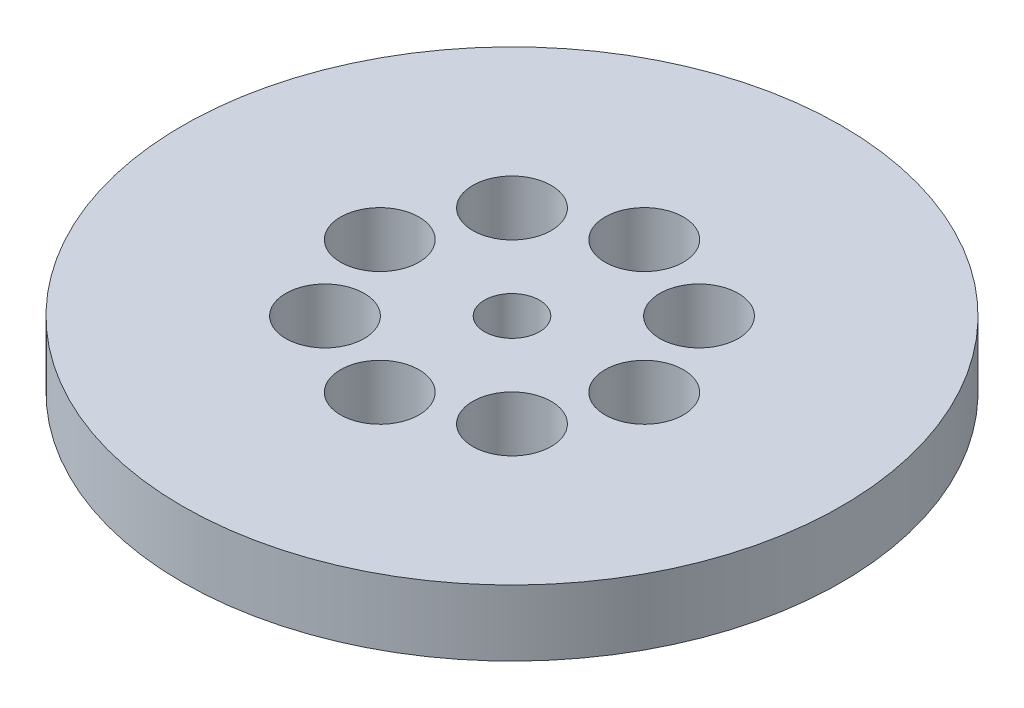
SolidWorks part; units mm, degrees
ref_plane "Front Plane" through (0, 0, 0) normal (0, 0, 1) x (1, 0, 0)
ref_plane "Top Plane" through (0, 0, 0) normal (0, 1, 0) x (1, 0, 0)
ref_plane "Right Plane" through (0, 0, 0) normal (1, 0, 0) x (0, 0, -1)
sketch "Sketch1" plane through (0, 0, 0) normal (0, 1, 0) x (1, 0, 0)
  circle A0 centre (0, 0) radius 60
  dimension "FLANGE_OD" = 120
extrude "Boss-Extrude1" add sketch "Sketch1" along normal blind 12
sketch "Sketch2" plane through (0, 0, 0) normal (0, 1, 0) x (1, 0, 0)
  circle A0 centre (0, 0) radius 5
  dimension "BORE_D" = 10
extrude "Cut-Extrude1" cut sketch "Sketch2" along normal through all
sketch "Sketch3" plane through (0, 12, 0) normal (0, 1, 0) x (1, 0, 0)
  circle A0 centre (0, 0) radius 24.0759 construction
  circle A1 centre (-24.0759, 0) radius 7.1381
  dimension "BOLT_D" = 14.2762
  dimension "BOLT_PCD" = 48.1518
extrude "Cut-Extrude2" cut sketch "Sketch3" against normal blind 10.7814
pattern_circular "CirPattern1" count 8 over 360 about axis through (0, 0, 0) along (0, 1, 0) of "Cut-Extrude2"
